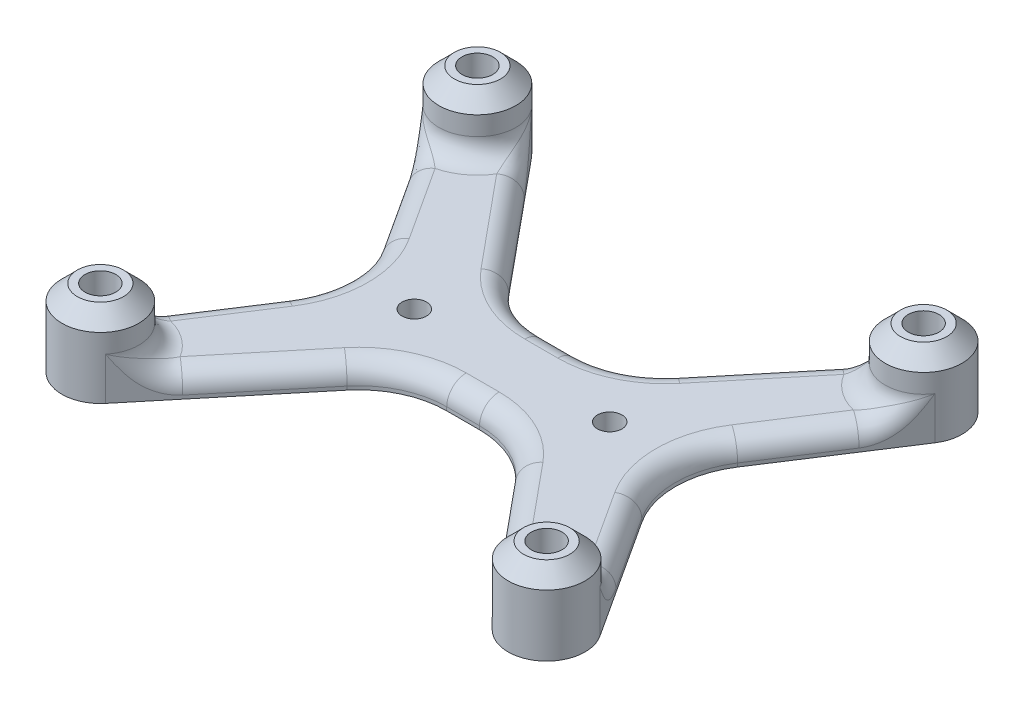
SolidWorks part; units mm, degrees
ref_plane "Front Plane" through (0, 0, 0) normal (0, 0, 1) x (1, 0, 0)
ref_plane "Top Plane" through (0, 0, 0) normal (0, 1, 0) x (1, 0, 0)
ref_plane "Right Plane" through (0, 0, 0) normal (1, 0, 0) x (0, 0, -1)
sketch "Sketch1" plane through (0, 0, 0) normal (0, 1, 0) x (1, 0, 0)
  line L0 (-7.5163, 6.35) -> (7.5163, 6.35)
  line L1 (-29, -24.5) -> (29, -24.5) construction
  line L2 (-29, -24.5) -> (-29, 24.5) construction
  line L3 (-29, 24.5) -> (29, 24.5) construction
  line L4 (29, -24.5) -> (29, 24.5) construction
  line L5 (-29, -24.5) -> (29, 24.5) construction
  line L6 (-29, 24.5) -> (29, -24.5) construction
  line L7 (-19.05, -6.35) -> (19.05, -6.35) construction
  line L8 (-19.05, -6.35) -> (-19.05, 6.35) construction
  line L9 (-19.05, 6.35) -> (19.05, 6.35) construction
  line L10 (19.05, -6.35) -> (19.05, 6.35) construction
  line L11 (-19.05, -6.35) -> (19.05, 6.35) construction
  line L12 (-19.05, 6.35) -> (19.05, -6.35) construction
  line L13 (7.5163, 6.35) -> (25.1456, 27.6849)
  line L14 (19.05, 0) -> (33.1932, 21.7766)
  line L15 (19.05, 0) -> (33.1932, -21.7766)
  line L16 (25.1456, -27.6849) -> (7.5163, -6.35)
  line L17 (7.5163, -6.35) -> (-7.5163, -6.35)
  line L18 (-7.5163, -6.35) -> (-25.1456, -27.6849)
  line L19 (-19.05, 0) -> (-33.1932, -21.7766)
  line L20 (-19.05, 0) -> (-33.1932, 21.7766)
  line L21 (-25.1456, 27.6849) -> (-7.5163, 6.35)
  circle A0 centre (-29, -24.5) radius 5
  circle A1 centre (29, -24.5) radius 5
  circle A2 centre (29, 24.5) radius 5
  circle A3 centre (-29, 24.5) radius 5
  point P0 (0, 0)
  point P6 (0, 0)
  point P30 (-8.0209, 6.35)
  dimension "D5" = 10
  dimension "D6" = 10
  dimension "D7" = 10
  dimension "D8" = 10
  dimension "D1" = 12.7
  dimension "D2" = 38.1
  dimension "D3" = 58
  dimension "D4" = 49
extrude "Boss-Extrude1" add sketch "Sketch1" along normal blind 3 contours A0 | A3 L20 L19 A0 L18 L17 L16 A1 L15 L14 A2 L13 L0 L21 | A3 | A2 | A1 region at (0, 0, 0) region at (-29, 0, -24.5) region at (29, 0, -24.5) region at (-29, 0, 24.5) region at (29, 0, 24.5)
sketch "Sketch2" plane through (0, 3, 0) normal (0, 1, 0) x (1, 0, 0)
  circle A0 centre (-29, -24.5) radius 5
  circle A1 centre (29, -24.5) radius 5
  circle A2 centre (29, 24.5) radius 5
  circle A3 centre (-29, 24.5) radius 5
extrude "Boss-Extrude2" add sketch "Sketch2" along normal blind 7
sketch "Sketch3" plane through (0, 10, 0) normal (0, 1, 0) x (1, 0, 0)
  circle A0 centre (-29, -24.5) radius 2
  circle A1 centre (-29, 24.5) radius 2
  circle A2 centre (29, 24.5) radius 2
  circle A3 centre (29, -24.5) radius 2
  dimension "D1" = 4
  dimension "D2" = 4
  dimension "D3" = 4
  dimension "D4" = 4
extrude "Cut-Extrude1" cut sketch "Sketch3" against normal blind 4.8
fillet "Fillet2" radius 11.43 4 edges at (7.5163, 1.5, -6.35) (-7.5163, 1.5, -6.35) (7.5163, 1.5, 6.35) (-7.5163, 1.5, 6.35)
fillet "Fillet3" radius 11.43 2 edges at (-19.05, 1.5, 0) (19.05, 1.5, 0)
fillet "Fillet4" radius 2.54 4 edges at (-26.041, 3, 20.4696) (26.041, 3, 20.4696) (26.041, 3, -20.4696) (-26.041, 3, -20.4696)
fillet "Fillet5" radius 2.54 24 edges at (31.0686, 3.3005, 18.5052) (26.6063, 3, 11.6346) (31.0686, 3.3005, -18.5052) (26.6063, 3, -11.6346) (-22.6609, 3.3005, 24.6779) (-16.2478, 3, 16.9168) (-7.0034, 3, 7.4392) (0, 3, 6.35) (22.6609, 3.3005, 24.6779) (16.2478, 3, 16.9168) (-31.0686, 3.3005, -18.5052) (-26.6063, 3, -11.6346) (-31.0686, 3.3005, 18.5052) (-26.6063, 3, 11.6346) (-22.6609, 3.3005, -24.6779) (-16.2478, 3, -16.9168) (-7.0034, 3, -7.4392) (0, 3, -6.35) (7.0034, 3, -7.4392) (22.6609, 3.3005, -24.6779) (21.2491, 3, 0) (7.0034, 3, 7.4392) (-21.2491, 3, 0) (16.2478, 3, -16.9168)
sketch "Sketch4" plane through (0, 3, 0) normal (0, 1, 0) x (1, 0, 0)
  circle A0 centre (-12.7, 0) radius 1.5875
  circle A1 centre (12.7, 0) radius 1.5875
  dimension "D1" = 3.175
  dimension "D3" = 3.175
  dimension "D2" = 12.7
  dimension "D4" = 12.7
extrude "Cut-Extrude2" cut sketch "Sketch4" against normal through all
chamfer "Chamfer1" distance 2 angle 45 4 edges at (-29, 10, 29.5) (-29, 10, -19.5) (29, 10, -19.5) (29, 10, 29.5)
